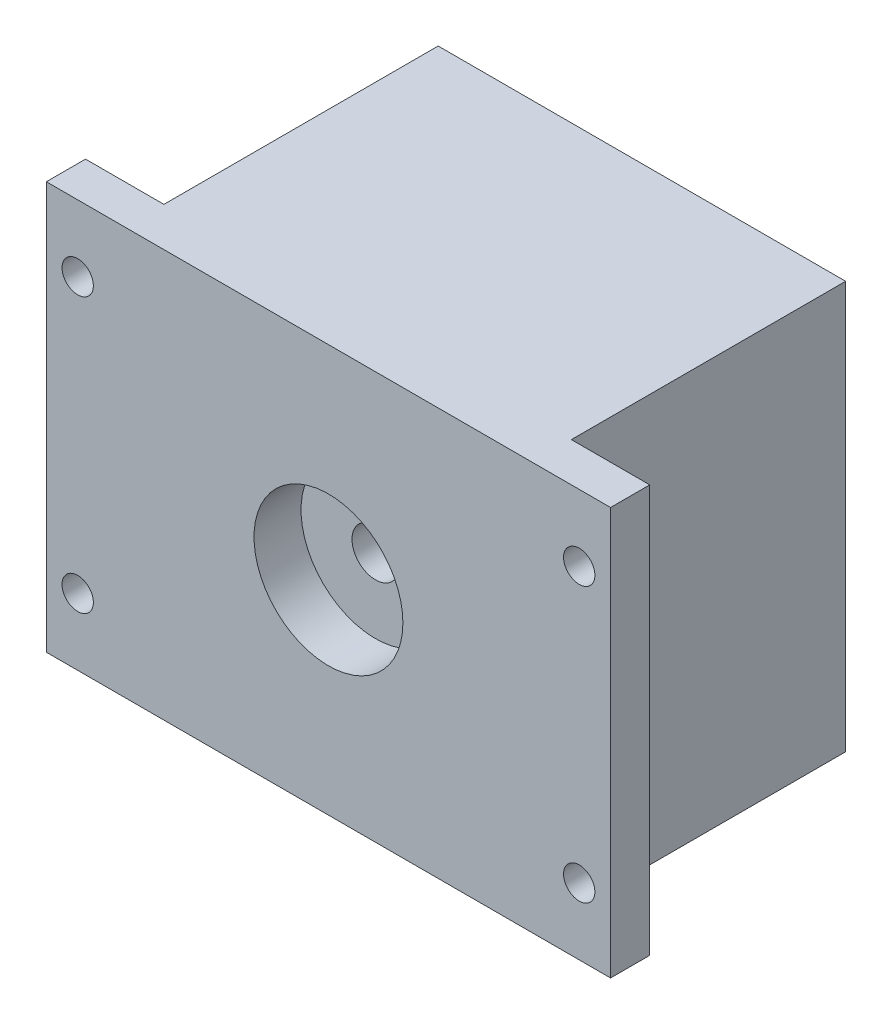
SolidWorks part; units mm, degrees
ref_plane "Front Plane" through (0, 0, 0) normal (0, 0, 1) x (1, 0, 0)
ref_plane "Top Plane" through (0, 0, 0) normal (0, 1, 0) x (1, 0, 0)
ref_plane "Right Plane" through (0, 0, 0) normal (1, 0, 0) x (0, 0, -1)
sketch "Sketch3" plane through (0, 0, 0) normal (0, 0, 1) x (1, 0, 0)
  line L1 (26, -26) -> (-26, -26)
  line L2 (26, -26) -> (26, 26)
  line L3 (26, 26) -> (-26, 26)
  line L4 (-26, -26) -> (-26, 26)
  line L5 (26, -26) -> (-26, 26) construction
  line L6 (26, 26) -> (-26, -26) construction
  circle A0 centre (0, 0) radius 9.5
  point P0 (0, 0)
extrude "Boss-Extrude1" add sketch "Sketch3" along normal blind 40 contours L2 L1 L4 L3
sketch "Sketch4" plane through (0, 0, 40) normal (0, 0, 1) x (1, 0, 0)
  line L0 (0, 0) -> (0, -26) construction
  line L1 (26, -26) -> (-26, -26) construction
  line L2 (0, -26) -> (0, 0) construction
  line L3 (0, 0) -> (0, 26) construction
  line L4 (26, 26) -> (-26, 26) construction
  line L5 (0, 26) -> (0, 0) construction
  line L6 (0, 0) -> (-26, 0) construction
  line L7 (-26, -26) -> (-26, 26) construction
  line L8 (-26, 0) -> (0, 0) construction
  line L9 (0, 0) -> (26, 0) construction
  line L10 (26, -26) -> (26, 26) construction
  line L11 (0, 0) -> (0, -26) construction
  line L12 (0, -26) -> (0, 26) construction
  line L13 (-26, 0) -> (26, 0) construction
  circle A0 centre (0, 0) radius 9.5
  circle A1 centre (0, 0) radius 3
  circle A2 centre (0, 0) radius 3
extrude "Cut-Extrude5" cut sketch "Sketch4" against normal blind 40 contours A1
extrude "Cut-Extrude6" cut sketch "Sketch4<5>" against normal blind 6 contours A0 A1 region at (-9.2313, 0, 40)
sketch "Sketch4<5>" plane through (0, 0, 40) normal (0, 0, 1) x (1, 0, 0) same geometry as "Sketch4"
sketch "Sketch5" plane through (0, 0, 0) normal (0, 0, -1) x (-1, 0, 0)
  circle A0 centre (0, 0) radius 9.5
extrude "Cut-Extrude8" cut sketch "Sketch5" against normal blind 6
sketch "Sketch6" plane through (0, 0, 40) normal (0, 0, 1) x (1, 0, 0)
  line L0 (26, -26) -> (-26, -26) construction
  line L1 (26, 26) -> (36, 26)
  line L2 (26, 26) -> (26, -26)
  line L3 (26, -26) -> (36, -26)
  line L4 (36, 26) -> (36, -26)
  line L5 (-26, 26) -> (-36, 26)
  line L6 (-26, 26) -> (-26, -26)
  line L7 (-26, -26) -> (-36, -26)
  line L8 (-36, 26) -> (-36, -26)
  dimension "D1" = 10
  dimension "D2" = 10
extrude "Boss-Extrude2" add sketch "Sketch6" against normal blind 5
sketch "Sketch7" plane through (0, 0, 35) normal (0, 0, -1) x (-1, 0, 0)
  line L1 (-32, -17.5) -> (32, -17.5) construction
  line L2 (-32, -17.5) -> (-32, 17.5) construction
  line L3 (-32, 17.5) -> (32, 17.5) construction
  line L4 (32, -17.5) -> (32, 17.5) construction
  line L5 (-32, -17.5) -> (32, 17.5) construction
  line L6 (-32, 17.5) -> (32, -17.5) construction
  circle A0 centre (-32, 17.5) radius 2
  circle A1 centre (32, 17.5) radius 2
  circle A2 centre (32, -17.5) radius 2
  circle A3 centre (-32, -17.5) radius 2
  point P0 (0, 0)
  dimension "D3" = 4
  dimension "D4" = 4
  dimension "D5" = 4
  dimension "D6" = 4
  dimension "D1" = 64
  dimension "D2" = 35
extrude "Cut-Extrude9" cut sketch "Sketch7" against normal blind 5
